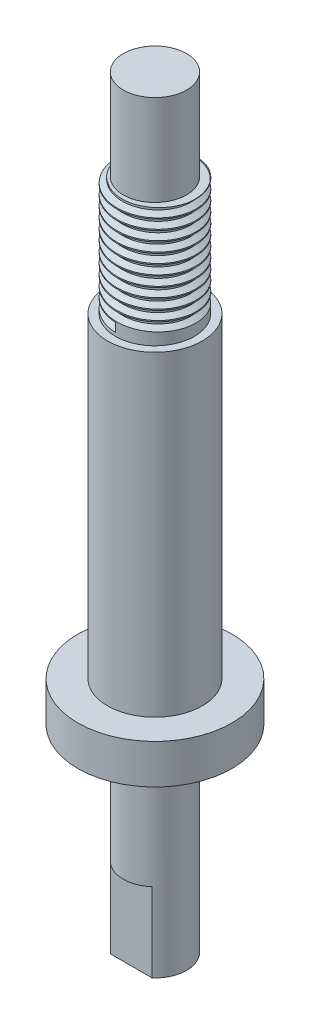
SolidWorks part; units mm, degrees
ref_plane "Front Plane" through (0, 0, 0) normal (0, 0, 1) x (1, 0, 0)
ref_plane "Top Plane" through (0, 0, 0) normal (0, 1, 0) x (1, 0, 0)
ref_plane "Right Plane" through (0, 0, 0) normal (1, 0, 0) x (0, 0, -1)
sketch "Sketch1" plane through (0, 0, 0) normal (0, 1, 0) x (1, 0, 0)
  circle A0 centre (0, 0) radius 9.75
  dimension "D1" = 19.5
extrude "Boss-Extrude1" add sketch "Sketch1" along normal blind 5
sketch "Sketch2" plane through (0, 5, 0) normal (0, 1, 0) x (1, 0, 0)
  circle A0 centre (0, 0) radius 6
  dimension "D1" = 12
extrude "Boss-Extrude2" add sketch "Sketch2" along normal blind 40
sketch "Sketch3" plane through (0, 45, 0) normal (0, 1, 0) x (1, 0, 0)
  circle A0 centre (0, 0) radius 4
  dimension "D1" = 8
extrude "Boss-Extrude3" add sketch "Sketch3" along normal blind 26.5
sketch "Sketch4" plane through (0, 0, 0) normal (0, -1, 0) x (1, 0, 0)
  circle A0 centre (0, 0) radius 4
  dimension "D1" = 8
extrude "Boss-Extrude4" add sketch "Sketch4" along normal blind 25
sketch "Sketch5" plane through (0, -25, 0) normal (0, -1, 0) x (1, 0, 0)
  line L0 (-2.6458, 3) -> (2.6458, 3)
  arc A0 (2.6458, 3) -> (-2.6458, 3) centre (0, 0) ccw
  dimension "D2" = 8
  dimension "D1" = 3
extrude "Cut-Extrude1" cut sketch "Sketch5" against normal blind 10
sketch "Sketch10" plane through (0, 45, 0) normal (0, 1, 0) x (1, 0, 0)
  circle A0 centre (0, 0) radius 4
  circle A1 centre (0, 0) radius 5
  dimension "D1" = 10
  dimension "D2" = 8
extrude "Boss-Extrude5" add sketch "Sketch10" along normal blind 15
ref_plane "Plane1" through (0, 46, 0) normal (0, 1, 0) x (1, 0, 0)
sketch "Sketch11" plane through (0, 46, 0) normal (0, 1, 0) x (1, 0, 0)
  circle A0 centre (0, 0) radius 5
curve "Helix/Spiral1" pitch 1.25 height 15.3125 turns 12.25
ref_plane "Plane3" through (-5, 61.3125, 0) normal (0, 0.0398, -0.9992) x (-1, 0, 0)
sketch "Sketch14" plane through (-5, 61.3125, 0) normal (0, 0.0398, -0.9992) x (-1, 0, 0)
  line L0 (0.0126, 0.5419) -> (0.0126, -0.5748)
  line L1 (0.0126, -0.5748) -> (-0.6774, -0.1764)
  line L2 (-0.6774, 0.1436) -> (0.0126, 0.5419)
  line L3 (-0.6774, 0.1436) -> (-0.6774, -0.1764)
  point P2 (0.0126, -0.0164)
  dimension "D1" = 60
  dimension "D2" = 60
  dimension "D3" = 0.32
  dimension "D4" = 0.69
sweep "Cut-Sweep1" cut profiles "Sketch14" path "Helix/Spiral1"
